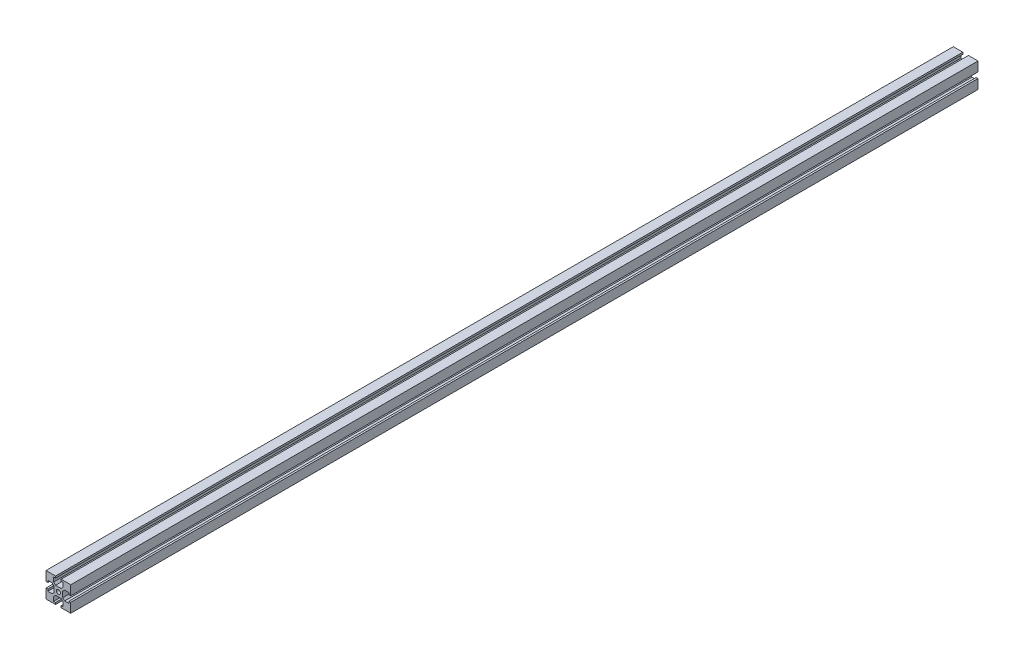
SolidWorks part; units mm, degrees
ref_plane "正面" through (0, 0, 0) normal (0, 0, 1) x (1, 0, 0)
ref_plane "平面" through (0, 0, 0) normal (0, 1, 0) x (1, 0, 0)
ref_plane "右側面" through (0, 0, 0) normal (1, 0, 0) x (0, 0, -1)
sketch "ｽｹｯﾁ2" plane through (0, 0, 0) normal (0, 0, 1) x (1, 0, 0)
  line L0 (0, 0) -> (0, 7.5) construction
  line L1 (-7.5, -7.5) -> (7.5, -7.5) construction
  line L2 (-7.5, -7.5) -> (-7.5, 7.5) construction
  line L3 (-7.5, 7.5) -> (7.5, 7.5) construction
  line L4 (7.5, -7.5) -> (7.5, 7.5) construction
  line L5 (-7.5, -7.5) -> (7.5, 7.5) construction
  line L6 (-7.5, 7.5) -> (7.5, -7.5) construction
  line L8 (1.7, 2.65) -> (-1.7, 2.65)
  line L9 (-2.85, 3.8) -> (2.85, 3.8) construction
  line L10 (-2.85, 6.4) -> (-2.85, 3.8)
  line L11 (2.85, 6.4) -> (2.85, 3.8)
  line L12 (-2.85, 3.8) -> (-1.7, 2.65)
  line L13 (1.7, 2.65) -> (2.85, 3.8)
  line L14 (-2.85, 6.4) -> (-1.7, 6.4)
  line L15 (-1.7, 6.4) -> (-1.7, 7.5)
  line L16 (-1.7, 7.5) -> (-7.5, 7.5)
  line L17 (2.85, 6.4) -> (1.7, 6.4)
  line L18 (1.7, 6.4) -> (1.7, 7.5)
  line L19 (1.7, 7.5) -> (7.5, 7.5)
  line L20 (3.8, 2.85) -> (2.65, 1.7)
  line L21 (2.65, -1.7) -> (2.65, 1.7)
  line L22 (2.65, -1.7) -> (3.8, -2.85)
  line L23 (6.4, -2.85) -> (6.4, -1.7)
  line L24 (6.4, -2.85) -> (3.8, -2.85)
  line L25 (6.4, -1.7) -> (7.5, -1.7)
  line L26 (7.5, -1.7) -> (7.5, -7.5)
  line L27 (6.4, 1.7) -> (7.5, 1.7)
  line L28 (7.5, 1.7) -> (7.5, 7.5)
  line L29 (6.4, 2.85) -> (6.4, 1.7)
  line L30 (6.4, 2.85) -> (3.8, 2.85)
  line L31 (2.85, -3.8) -> (1.7, -2.65)
  line L32 (-1.7, -2.65) -> (1.7, -2.65)
  line L33 (-1.7, -2.65) -> (-2.85, -3.8)
  line L34 (-2.85, -6.4) -> (-1.7, -6.4)
  line L35 (-2.85, -6.4) -> (-2.85, -3.8)
  line L36 (-1.7, -6.4) -> (-1.7, -7.5)
  line L37 (-1.7, -7.5) -> (-7.5, -7.5)
  line L38 (1.7, -6.4) -> (1.7, -7.5)
  line L39 (1.7, -7.5) -> (7.5, -7.5)
  line L40 (2.85, -6.4) -> (1.7, -6.4)
  line L41 (2.85, -6.4) -> (2.85, -3.8)
  line L42 (-3.8, -2.85) -> (-2.65, -1.7)
  line L43 (-2.65, 1.7) -> (-2.65, -1.7)
  line L44 (-2.65, 1.7) -> (-3.8, 2.85)
  line L45 (-6.4, 2.85) -> (-6.4, 1.7)
  line L46 (-6.4, 2.85) -> (-3.8, 2.85)
  line L47 (-6.4, 1.7) -> (-7.5, 1.7)
  line L48 (-7.5, 1.7) -> (-7.5, 7.5)
  line L49 (-6.4, -1.7) -> (-7.5, -1.7)
  line L50 (-7.5, -1.7) -> (-7.5, -7.5)
  line L51 (-6.4, -2.85) -> (-6.4, -1.7)
  line L52 (-6.4, -2.85) -> (-3.8, -2.85)
  circle A0 centre (0, 0) radius 1.25
  point P0 (0, 0)
  point P11 (0, 7.5)
  point P14 (0, 2.65)
  point P17 (0, 3.8)
  dimension "D8" = 2.5
  dimension "D1" = 15
  dimension "D2" = 3.4
  dimension "D3" = 1.1
  dimension "D4" = 2.6
  dimension "D5" = 5.7
  dimension "D6" = 3.4
  dimension "D7" = 4
extrude "ﾎﾞｽ - 押し出し1" add sketch "ｽｹｯﾁ2" along normal blind 550
